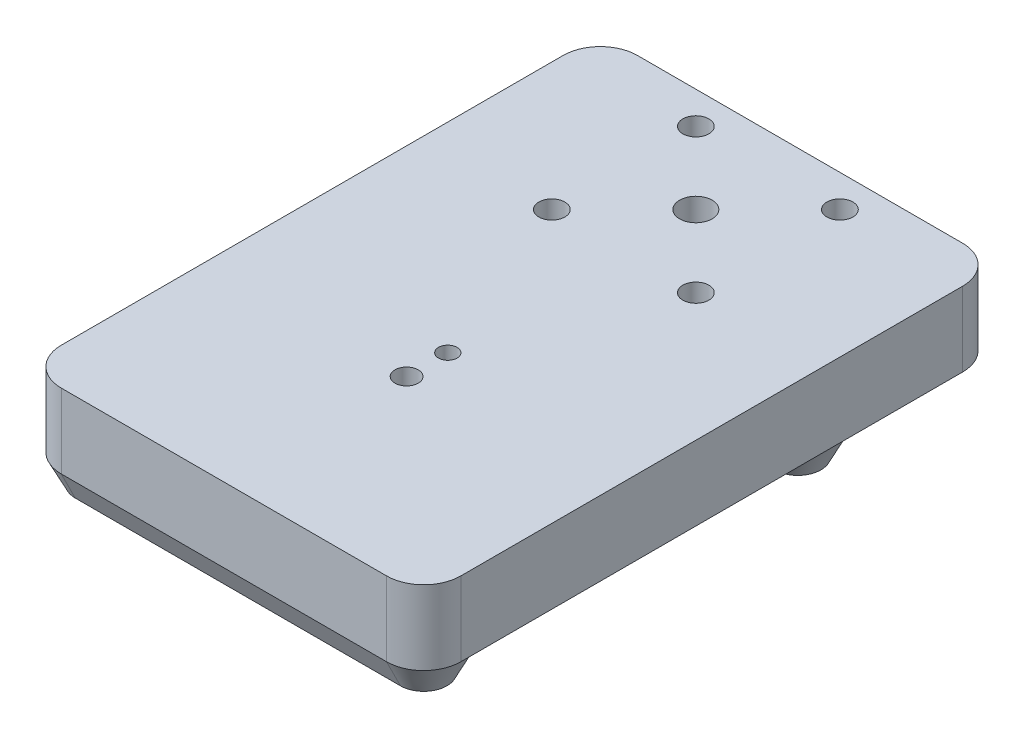
SolidWorks part; units mm, degrees
ref_plane "Front Plane" through (0, 0, 0) normal (0, 0, 1) x (1, 0, 0)
ref_plane "Top Plane" through (0, 0, 0) normal (0, 1, 0) x (1, 0, 0)
ref_plane "Right Plane" through (0, 0, 0) normal (1, 0, 0) x (0, 0, -1)
sketch "Sketch1" plane through (0, 0, 0) normal (0, 1, 0) x (1, 0, 0)
  line L1 (-35, 62) -> (35, 62)
  line L2 (-43, 54) -> (-43, -54)
  line L3 (-35, -62) -> (35, -62)
  line L4 (43, 54) -> (43, -54)
  line L5 (-43, 62) -> (43, -62) construction
  line L6 (-43, -62) -> (43, 62) construction
  arc A0 (-43, -54) -> (-35, -62) centre (-35, -54) ccw
  arc A1 (-35, 62) -> (-43, 54) centre (-35, 54) ccw
  arc A2 (43, 54) -> (35, 62) centre (35, 54) ccw
  arc A3 (43, -54) -> (35, -62) centre (35, -54) cw
  point P0 (0, 0)
  dimension "D3" = 8
  dimension "D4" = 8
  dimension "D1" = 124
  dimension "D2" = 86
extrude "Boss-Extrude1" add sketch "Sketch1" along normal blind 16
sketch "Sketch17" plane through (0, 0, 0) normal (0, -1, 0) x (-1, 0, 0)
  line L0 (-35, -54) -> (35, -54) construction
  line L1 (-35, -49) -> (35, -49)
  line L2 (-35, -59) -> (35, -59)
  line L3 (-43, -54) -> (-43, 54) construction
  line L4 (35, -62) -> (-35, -62) construction
  line L5 (43, 54) -> (43, -54) construction
  arc A0 (-35, -49) -> (-35, -59) centre (-35, -54) ccw
  arc A1 (35, -59) -> (35, -49) centre (35, -54) ccw
  circle A2 centre (35, 26.5) radius 5
  circle A3 centre (-35, 26.5) radius 5
  point P2 (0, -54)
  dimension "D5" = 10
  dimension "D1" = 10
  dimension "D2" = 8
  dimension "D3" = 8
  dimension "D4" = 8
  dimension "D6" = 80.5
  dimension "D7" = 8
  dimension "D8" = 8
extrude "Boss-Extrude2" add sketch "Sketch17" along normal blind 6
sketch "Sketch12" plane through (43, 0, 0) normal (1, 0, 0) x (0, 0, -1)
  line L0 (-54, 0) -> (54, 0) construction
  line L1 (-18.42, 0) -> (-9.22, 0)
  line L2 (-18.42, 0) -> (-18.42, 6)
  line L3 (-18.42, 6) -> (-9.22, 6)
  line L4 (-9.22, 0) -> (-9.22, 6)
  point P8 (-13.82, 0)
  dimension "D1" = 6
  dimension "D2" = 9.2
extrude "Cut-Extrude4" [suppressed] cut sketch "Sketch12" against normal up to surface (86 mm away) contours L3 L4 L1 L2
sketch "Sketch14" plane through (0, 16, 0) normal (0, 1, 0) x (1, 0, 0)
  circle A2 centre (0, 39.57) radius 3.5
  circle A3 centre (0, 39.57) radius 3.5
  dimension "D1" = 1
extrude "Cut-Extrude7" cut sketch "Sketch14" against normal up to next
sketch "Sketch16" plane through (0, 0, 0) normal (0, -1, 0) x (-1, 0, 0)
  line L1 (-40, -18.82) -> (40, -18.82)
  line L2 (-40, -18.82) -> (-40, -8.82)
  line L3 (-40, -8.82) -> (40, -8.82)
  line L4 (40, -18.82) -> (40, -8.82)
  line L5 (-43, -54) -> (-43, 54) construction
  point P5 (-40, -13.82)
  dimension "D1" = 10
  dimension "D2" = 80
  dimension "D3" = 3
extrude "Cut-Extrude8" cut sketch "Sketch16" against normal blind 9.5
chamfer "Chamfer3" distance 3 distance2 6 6 edges at (40, 0, 54) (0, 0, 59) (0, 0, 49) (-40, 0, 54) (-35, 0, -21.5) (35, 0, -21.5) first distance on face at (0, 0, 13.82)
hole_wizard "CBORE for M3 SHCS1" positions "Sketch18" profile "Sketch19" counterbore size "M3" standard "ANSI Metric" end condition through all
sketch "Sketch18" plane through (0, 16, 0) normal (0, 1, 0) x (1, 0, 0)
  point P2 (-15.5, 55.07)
  point P5 (-15.5, 24.07)
  point P8 (15.5, 24.07)
  point P11 (15.5, 55.07)
sketch "Sketch19" plane through (-15.5, 16, -55.07) normal (1, 0, 0) x (0, 0, 1)
  line L0 (0, 0) -> (0, 22)
  line L1 (0, 22) -> (1.6, 22)
  line L3 (1.6, 22) -> (1.6, 4)
  line L4 (1.6, 4) -> (2.8, 4)
  line L5 (2.8, 4) -> (2.8, 0)
  line L7 (2.8, 0) -> (0, 0)
  line L11 (0, -6.35) -> (0, 107.95) construction
  dimension "Thru Hole Dia." = 3.2
  dimension "Thru Hole Depth" = 22
  dimension "C'Bore Dia." = 5.6
  dimension "C'Bore Depth" = 4
chamfer "Chamfer4" distance 10 angle 58 2 edges at (40, 9.5, 13.82) (-40, 9.5, 13.82) first distance on face at (40, 4.75, 13.82) first distance on face at (-40, 4.75, 13.82)
hole_wizard "Ø5.0mm Dowel Hole1" positions "Sketch20" profile "Sketch21" hole size "Ø5.0" standard "ANSI Metric"
sketch "Sketch20" plane through (0, -6, 0) normal (0, 1, 0) x (1, 0, 0)
  point P0 (-35, -54)
  point P3 (35, -54)
  point P6 (-35, 26.5)
  point P9 (35, 26.5)
sketch "Sketch21" plane through (-35, -6, 54) normal (1, 0, 0) x (0, 0, -1)
  line L0 (0, 0) -> (0, 19)
  line L1 (0, 19) -> (2.5, 19)
  line L2 (2.5, 19) -> (2.5, 0)
  line L5 (2.5, 0) -> (0, 0)
  line L10 (0, 19) -> (-2.5, 19) construction
  line L11 (0, -6.35) -> (0, 107.95) construction
  dimension "Hole Dia." = 5
  dimension "Hole Depth" = 19
  dimension "Drill Angle" = 180
hole_wizard "Ø4.0mm Dowel Hole1" positions "Sketch22" profile "Sketch23" hole size "Ø4.0" standard "ANSI Metric" end condition through all
sketch "Sketch22" plane through (0, 16, 0) normal (0, 1, 0) x (1, 0, 0)
  line L0 (0, -0.5598) -> (0, -19.841) construction
  line L2 (23.9967, -18.82) -> (-23.9967, -18.82) construction
  point P0 (0, -13.82)
  dimension "D1" = 5
sketch "Sketch23" plane through (0, 16, 13.82) normal (1, 0, 0) x (0, 0, 1)
  line L0 (0, 0) -> (0, 22)
  line L1 (0, 22) -> (2, 22)
  line L2 (2, 22) -> (2, 0)
  line L5 (2, 0) -> (0, 0)
  line L11 (0, -6.35) -> (0, 107.95) construction
  dimension "Thru Hole Dia." = 4
  dimension "Thru Hole Depth" = 22
hole_wizard "Ø5.0mm Dowel Hole2" positions "Sketch24" profile "Sketch25" hole size "Ø5.0" standard "ANSI Metric" end condition through all
sketch "Sketch24" plane through (0, 16, 0) normal (0, 1, 0) x (1, 0, 0)
  point P0 (0, -22.68)
sketch "Sketch25" plane through (0, 16, 22.68) normal (1, 0, 0) x (0, 0, 1)
  line L0 (0, 0) -> (0, 22)
  line L1 (0, 22) -> (2.5, 22)
  line L2 (2.5, 22) -> (2.5, 0)
  line L5 (2.5, 0) -> (0, 0)
  line L11 (0, -6.35) -> (0, 107.95) construction
  dimension "Thru Hole Dia." = 5
  dimension "Thru Hole Depth" = 22
fillet "Fillet2" radius 5 2 edges at (-39.1998, 0, 13.82) (39.1998, 0, 13.82)
sketch "Sketch26" plane through (0, 0, 0) normal (0, -1, 0) x (1, 0, 0)
  line L8 (22.15, -80.72) -> (-22.15, -80.72)
  line L9 (-17.15, -60.72) -> (17.15, -60.72) construction
  line L16 (-22.15, -22.0058) -> (-22.15, -57.1342)
  line L17 (-17.5642, -17.42) -> (-22.15, -22.0058)
  line L18 (17.5642, -17.42) -> (-17.5642, -17.42)
  line L19 (22.15, -22.0058) -> (17.5642, -17.42)
  line L20 (22.15, -57.1342) -> (22.15, -22.0058)
  line L21 (17.5642, -61.72) -> (22.15, -57.1342)
  line L22 (-17.5642, -61.72) -> (17.5642, -61.72)
  line L23 (-22.15, -57.1342) -> (-17.5642, -61.72)
  line L24 (-22.15, -22.0058) -> (-22.15, -80.72)
  line L25 (-17.5642, -17.42) -> (-22.15, -22.0058)
  line L26 (17.5642, -17.42) -> (-17.5642, -17.42)
  line L27 (22.15, -22.0058) -> (17.5642, -17.42)
  line L28 (22.15, -80.72) -> (22.15, -22.0058)
  dimension "D2" = 20
  dimension "D1" = 1
extrude "Cut-Extrude9" cut sketch "Sketch26" against normal offset from surface (6 mm away) 10 up to face at (0, 16, 25.18)
fillet "Fillet3" radius 4 2 edges at (-22.15, 3, -62) (22.15, 3, -62)
sketch "Sketch13" plane through (0, 6, 0) normal (0, -1, 0) x (1, 0, 0)
  circle A0 centre (0, -39.57) radius 11.5 construction
  circle A1 centre (0, -39.57) radius 11.5
extrude "Cut-Extrude6" cut sketch "Sketch13" against normal blind 3
sketch "Sketch28" plane through (0, 0, 0) normal (0, -1, 0) x (-1, 0, 0)
  line L1 (4.9652, -22.68) -> (2.4826, -18.38)
  line L2 (2.4826, -18.38) -> (-2.4826, -18.38)
  line L3 (-2.4826, -18.38) -> (-4.9652, -22.68)
  line L4 (-4.9652, -22.68) -> (-2.4826, -26.98)
  line L5 (-2.4826, -26.98) -> (2.4826, -26.98)
  line L6 (2.4826, -26.98) -> (4.9652, -22.68)
  circle A0 centre (0, -22.68) radius 4.3 construction
  dimension "D1" = 8.6
extrude "Cut-Extrude10" cut sketch "Sketch28" against normal blind 8
fillet "Fillet4" radius 2 5 edges at (-3.8509, 0, 20.75) (-3.7239, 0, 24.83) (0, 0, 26.98) (3.7239, 0, 24.83) (3.8509, 0, 20.75)
